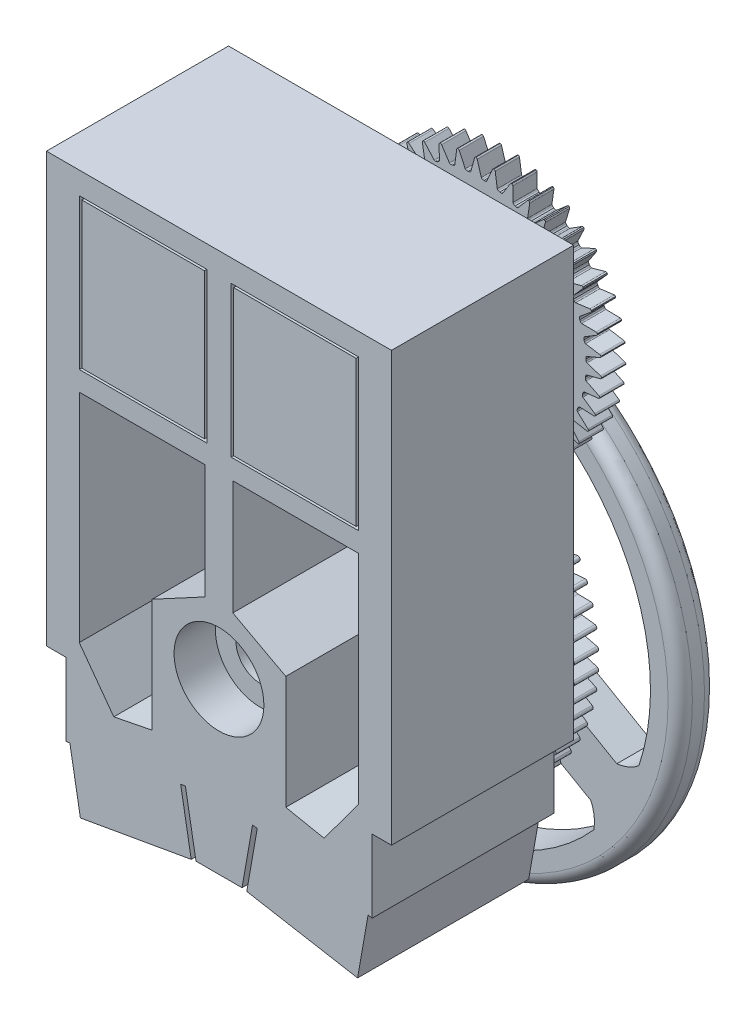
SolidWorks part; units mm, degrees
ref_plane "前视基准面" through (0, 0, 0) normal (0, 0, 1) x (1, 0, 0)
ref_plane "上视基准面" through (0, 0, 0) normal (0, 1, 0) x (1, 0, 0)
ref_plane "右视基准面" through (0, 0, 0) normal (1, 0, 0) x (0, 0, -1)
sketch "草图1" plane through (0, 0, 0) normal (0, 0, 1) x (1, 0, 0)
  line L0 (14.2131, -21.082) -> (12.6181, -21.082)
  line L2 (-11.5, 12.4) -> (-1, 12.4)
  line L3 (-11.5, 12.4) -> (-11.5, 0)
  line L4 (-11.5, 0) -> (-1, 0)
  line L5 (-1, 12.4) -> (-1, 0)
  line L6 (14.2131, 14.2258) -> (14.2131, -1.4738)
  line L7 (11.5, 0) -> (1, 0)
  line L8 (14.2131, 14.2258) -> (-14.2131, 14.2258)
  line L9 (-14.2131, 14.2258) -> (-14.2131, -1.4738)
  line L12 (1, 12.4) -> (1, 0)
  line L13 (11.5, 12.4) -> (1, 12.4)
  line L14 (11.5, 12.4) -> (11.5, 0)
  line L16 (14.2131, -1.4738) -> (14.2131, -21.082)
  line L18 (-14.2131, -1.4738) -> (-14.2131, -21.082)
  line L19 (-12.6181, -21.082) -> (-14.2131, -21.082)
  line L24 (-1.897, -30.2746) -> (1.897, -30.2746)
  line L29 (1.897, -30.2746) -> (2.7652, -25.3506)
  line L30 (2.7652, -25.3506) -> (12.6181, -27.0879)
  line L31 (12.6181, -27.0879) -> (12.6181, -21.082)
  line L32 (-1.897, -30.2746) -> (-2.7652, -25.3506)
  line L33 (-2.7652, -25.3506) -> (-12.6181, -27.0879)
  line L34 (-12.6181, -27.0879) -> (-12.6181, -21.082)
  circle A0 centre (0, -16.3459) radius 2
  point P8 (-1.6019, -21.082)
  dimension "D5" = 4
  dimension "D1" = 10.5
  dimension "D2" = 12.4
  dimension "D3" = 28.4262
  dimension "D4" = 0
  dimension "D6" = 5
extrude "凸台-拉伸1" add sketch "草图1" along normal blind 15
sketch "草图2" plane through (0, 0, 15) normal (0, 0, 1) x (1, 0, 0)
  circle A0 centre (0, -16.3459) radius 3.7
extrude "切除-拉伸1" cut sketch "草图2" against normal blind 3.4
sketch "草图3" plane through (0, 0, 0) normal (0, 0, -1) x (-1, 0, 0)
  circle A0 centre (0, -16.3459) radius 3.7
  dimension "D1" = 7.4
extrude "切除-拉伸2" cut sketch "草图3" against normal blind 3.4
sketch "草图4" plane through (0, 0, 15) normal (0, 0, 1) x (1, 0, 0)
  line L1 (-11.511, -1.6162) -> (-1.141, -1.6162)
  line L2 (-1.141, -1.6162) -> (-1.141, -11.0446)
  line L3 (-1.141, -11.0446) -> (-5.5022, -13.39)
  line L4 (-5.5022, -13.39) -> (-5.5022, -22.7344)
  line L5 (-5.5022, -22.7344) -> (-8.6655, -23.3615)
  line L6 (-11.511, -19.4847) -> (-11.511, -1.6162)
  line L7 (5.5022, -22.7344) -> (8.6655, -23.3615)
  line L8 (5.5022, -13.39) -> (5.5022, -22.7344)
  line L9 (1.141, -11.0446) -> (5.5022, -13.39)
  line L10 (1.141, -1.6162) -> (1.141, -11.0446)
  line L11 (11.511, -1.6162) -> (1.141, -1.6162)
  line L12 (11.511, -19.4847) -> (11.511, -1.6162)
  line L13 (11.511, -19.4847) -> (8.6655, -23.3615)
  line L14 (-11.511, -19.4847) -> (-8.6655, -23.3615)
extrude "切除-拉伸4" cut sketch "草图4" against normal blind 30
sketch "草图5" plane through (0, 0, 0) normal (0, 0, 1) x (1, 0, 0)
  line L0 (-11.3, 12.2) -> (-11.3, 0.2)
  line L5 (-11.3, 0.2) -> (-1.2, 0.2)
  line L6 (-1.2, 12.2) -> (-1.2, 0.2)
  line L7 (-11.3, 12.2) -> (-1.2, 12.2)
  line L9 (11.3, 12.2) -> (1.2, 12.2)
  line L10 (1.2, 12.2) -> (1.2, 0.2)
  line L11 (11.3, 0.2) -> (1.2, 0.2)
  line L12 (11.3, 12.2) -> (11.3, 0.2)
extrude "凸台-拉伸2" add sketch "草图5" along normal blind 15 separate body
sketch "草图6" plane through (0, 0, 0) normal (0, 0, -1) x (-1, 0, 0)
  line L5 (0.5574, -2.1882) -> (0.2083, -3.1894)
  line L6 (-0.5574, -2.1882) -> (-0.2083, -3.1894)
  line L7 (0.9255, -2.2075) -> (1.1681, -3.2397)
  line L9 (-0.9255, -2.2075) -> (-1.1681, -3.2397)
  line L10 (2.0343, -2.324) -> (1.5824, -3.2833)
  line L11 (2.3983, -2.3816) -> (2.5316, -3.4336)
  line L12 (3.4888, -2.6134) -> (2.9391, -3.5202)
  line L13 (3.8448, -2.7088) -> (3.8675, -3.769)
  line L14 (4.9051, -3.0534) -> (4.2637, -3.8977)
  line L15 (5.2492, -3.1854) -> (5.1609, -4.2421)
  line L16 (6.2677, -3.6389) -> (5.5415, -4.4116)
  line L17 (6.5961, -3.8062) -> (6.3978, -4.8479)
  line L18 (7.5616, -4.3637) -> (6.7586, -5.0562)
  line L19 (7.8707, -4.5644) -> (7.5647, -5.5797)
  line L20 (8.7727, -5.2197) -> (7.9017, -5.8245)
  line L21 (9.0591, -5.4517) -> (8.6486, -6.4294)
  line L22 (9.8876, -6.1977) -> (8.9582, -6.7081)
  line L23 (10.1483, -6.4583) -> (9.6378, -7.3877)
  line L24 (10.8943, -7.2868) -> (9.9166, -7.6973)
  line L25 (11.1262, -7.5732) -> (10.5214, -8.4442)
  line L26 (11.7815, -8.4752) -> (10.7663, -8.7813)
  line L27 (11.9823, -8.7843) -> (11.2897, -9.5873)
  line L28 (12.5397, -9.7498) -> (11.498, -9.9481)
  line L29 (12.707, -10.0782) -> (11.9343, -10.8044)
  line L30 (13.1605, -11.0967) -> (12.1038, -11.185)
  line L31 (13.2926, -11.4408) -> (12.4482, -12.0822)
  line L32 (13.6371, -12.5011) -> (12.5769, -12.4785)
  line L33 (13.7325, -12.8571) -> (12.8257, -13.4068)
  line L34 (13.9643, -13.9476) -> (12.9123, -13.8143)
  line L35 (14.0219, -14.3116) -> (13.0626, -14.7635)
  line L36 (14.1385, -15.4204) -> (13.1062, -15.1779)
  line L37 (14.1578, -15.7885) -> (13.1565, -16.1376)
  line L38 (14.1578, -16.9034) -> (13.1565, -16.5542)
  line L39 (14.1385, -17.2714) -> (13.1062, -17.514)
  line L40 (14.0219, -18.3802) -> (13.0626, -17.9283)
  line L41 (13.9643, -18.7442) -> (12.9123, -18.8776)
  line L42 (13.7325, -19.8347) -> (12.8257, -19.2851)
  line L43 (13.6371, -20.1907) -> (12.5769, -20.2134)
  line L44 (13.2926, -21.2511) -> (12.4482, -20.6096)
  line L45 (13.1605, -21.5951) -> (12.1038, -21.5068)
  line L46 (12.707, -22.6136) -> (11.9343, -21.8874)
  line L47 (12.5397, -22.942) -> (11.498, -22.7438)
  line L48 (11.9823, -23.9076) -> (11.2897, -23.1046)
  line L49 (11.7815, -24.2167) -> (10.7663, -23.9106)
  line L50 (11.1262, -25.1186) -> (10.5214, -24.2476)
  line L51 (10.8943, -25.405) -> (9.9166, -24.9945)
  line L52 (10.1483, -26.2336) -> (9.6378, -25.3041)
  line L53 (9.8876, -26.4942) -> (8.9582, -25.9837)
  line L54 (9.0591, -27.2402) -> (8.6486, -26.2625)
  line L55 (8.7727, -27.4721) -> (7.9017, -26.8673)
  line L56 (7.8707, -28.1274) -> (7.5647, -27.1122)
  line L57 (7.5616, -28.3282) -> (6.7586, -27.6356)
  line L58 (6.5961, -28.8856) -> (6.3978, -27.8439)
  line L59 (6.2677, -29.0529) -> (5.5415, -28.2802)
  line L60 (5.2492, -29.5064) -> (5.1609, -28.4497)
  line L61 (4.9051, -29.6385) -> (4.2637, -28.7941)
  line L62 (3.8448, -29.983) -> (3.8675, -28.9229)
  line L63 (3.4888, -30.0784) -> (2.9391, -29.1716)
  line L64 (2.3983, -30.3102) -> (2.5316, -29.2582)
  line L65 (2.0343, -30.3678) -> (1.5824, -29.4086)
  line L66 (0.9255, -30.4844) -> (1.1681, -29.4521)
  line L67 (0.5574, -30.5037) -> (0.2083, -29.5024)
  line L68 (-0.5574, -30.5037) -> (-0.2083, -29.5024)
  line L69 (-0.9255, -30.4844) -> (-1.1681, -29.4521)
  line L70 (-2.0343, -30.3678) -> (-1.5824, -29.4086)
  line L71 (-2.3983, -30.3102) -> (-2.5316, -29.2582)
  line L72 (-3.4888, -30.0784) -> (-2.9391, -29.1716)
  line L73 (-3.8448, -29.983) -> (-3.8675, -28.9229)
  line L74 (-4.9051, -29.6385) -> (-4.2637, -28.7941)
  line L75 (-5.2492, -29.5064) -> (-5.1609, -28.4497)
  line L76 (-6.2677, -29.0529) -> (-5.5415, -28.2802)
  line L77 (-6.5961, -28.8856) -> (-6.3978, -27.8439)
  line L78 (-7.5616, -28.3282) -> (-6.7586, -27.6356)
  line L79 (-7.8707, -28.1274) -> (-7.5647, -27.1122)
  line L80 (-8.7727, -27.4721) -> (-7.9017, -26.8673)
  line L81 (-9.0591, -27.2402) -> (-8.6486, -26.2625)
  line L82 (-9.8876, -26.4942) -> (-8.9582, -25.9837)
  line L83 (-10.1483, -26.2336) -> (-9.6378, -25.3041)
  line L84 (-10.8943, -25.405) -> (-9.9166, -24.9945)
  line L85 (-11.1262, -25.1186) -> (-10.5214, -24.2476)
  line L86 (-11.7815, -24.2167) -> (-10.7663, -23.9106)
  line L87 (-11.9823, -23.9076) -> (-11.2897, -23.1046)
  line L88 (-12.5397, -22.942) -> (-11.498, -22.7438)
  line L89 (-12.707, -22.6136) -> (-11.9343, -21.8874)
  line L90 (-13.1605, -21.5951) -> (-12.1038, -21.5068)
  line L91 (-13.2926, -21.2511) -> (-12.4482, -20.6096)
  line L92 (-13.6371, -20.1907) -> (-12.5769, -20.2134)
  line L93 (-13.7325, -19.8347) -> (-12.8257, -19.2851)
  line L94 (-13.9643, -18.7442) -> (-12.9123, -18.8776)
  line L95 (-14.0219, -18.3802) -> (-13.0626, -17.9283)
  line L96 (-14.1385, -17.2714) -> (-13.1062, -17.514)
  line L97 (-14.1578, -16.9034) -> (-13.1565, -16.5542)
  line L98 (-14.1578, -15.7885) -> (-13.1565, -16.1376)
  line L99 (-14.1385, -15.4204) -> (-13.1062, -15.1779)
  line L100 (-14.0219, -14.3116) -> (-13.0626, -14.7635)
  line L101 (-13.9643, -13.9476) -> (-12.9123, -13.8143)
  line L102 (-13.7325, -12.8571) -> (-12.8257, -13.4068)
  line L103 (-13.6371, -12.5011) -> (-12.5769, -12.4785)
  line L104 (-13.2926, -11.4408) -> (-12.4482, -12.0822)
  line L105 (-13.1605, -11.0967) -> (-12.1038, -11.185)
  line L106 (-12.707, -10.0782) -> (-11.9343, -10.8044)
  line L107 (-12.5397, -9.7498) -> (-11.498, -9.9481)
  line L108 (-11.9823, -8.7843) -> (-11.2897, -9.5873)
  line L109 (-11.7815, -8.4752) -> (-10.7663, -8.7813)
  line L110 (-11.1262, -7.5732) -> (-10.5214, -8.4442)
  line L111 (-10.8943, -7.2868) -> (-9.9166, -7.6973)
  line L112 (-10.1483, -6.4583) -> (-9.6378, -7.3877)
  line L113 (-9.8876, -6.1977) -> (-8.9582, -6.7081)
  line L114 (-9.0591, -5.4517) -> (-8.6486, -6.4294)
  line L115 (-8.7727, -5.2197) -> (-7.9017, -5.8245)
  line L116 (-7.8707, -4.5644) -> (-7.5647, -5.5797)
  line L117 (-7.5616, -4.3637) -> (-6.7586, -5.0562)
  line L118 (-6.5961, -3.8062) -> (-6.3978, -4.8479)
  line L119 (-6.2677, -3.6389) -> (-5.5415, -4.4116)
  line L120 (-5.2492, -3.1854) -> (-5.1609, -4.2421)
  line L121 (-4.9051, -3.0534) -> (-4.2637, -3.8977)
  line L122 (-3.8448, -2.7088) -> (-3.8675, -3.769)
  line L123 (-3.4888, -2.6134) -> (-2.9391, -3.5202)
  line L124 (-2.3983, -2.3816) -> (-2.5316, -3.4336)
  line L125 (-2.0343, -2.324) -> (-1.5824, -3.2833)
  arc A1 (-1.3589, -3.4171) -> (-1.1681, -3.2397) centre (-1.3815, -3.2014) ccw
  arc A2 (-0.9255, -2.2075) -> (-0.5574, -2.1882) centre (-0.7383, -2.2588) cw
  arc A3 (0, -3.3459) -> (-0.2083, -3.1894) centre (0, -3.129) cw
  arc A4 (0, -3.3459) -> (0.2083, -3.1894) centre (0, -3.129) ccw
  arc A5 (1.3589, -3.4171) -> (1.1681, -3.2397) centre (1.3815, -3.2014) cw
  arc A6 (0.5574, -2.1882) -> (0.9255, -2.2075) centre (0.7383, -2.2588) cw
  arc A7 (1.3589, -3.4171) -> (1.5824, -3.2833) centre (1.3815, -3.2014) ccw
  arc A8 (2.7029, -3.63) -> (2.5316, -3.4336) centre (2.7479, -3.4179) cw
  arc A9 (2.0343, -2.324) -> (2.3983, -2.3816) centre (2.2067, -2.4131) cw
  arc A10 (2.7029, -3.63) -> (2.9391, -3.5202) centre (2.7479, -3.4179) ccw
  arc A11 (4.0172, -3.9822) -> (3.8675, -3.769) centre (4.0842, -3.7759) cw
  arc A12 (3.4888, -2.6134) -> (3.8448, -2.7088) centre (3.651, -2.7201) cw
  arc A13 (4.0172, -3.9822) -> (4.2637, -3.8977) centre (4.0842, -3.7759) ccw
  arc A14 (5.2876, -4.4698) -> (5.1609, -4.2421) centre (5.3758, -4.2717) cw
  arc A15 (4.9051, -3.0534) -> (5.2492, -3.1854) centre (5.0553, -3.1764) cw
  arc A16 (5.2876, -4.4698) -> (5.5415, -4.4116) centre (5.3758, -4.2717) ccw
  arc A17 (6.5, -5.0876) -> (6.3978, -4.8479) centre (6.6084, -4.8998) cw
  arc A18 (6.2677, -3.6389) -> (6.5961, -3.8062) centre (6.4042, -3.7769) cw
  arc A19 (6.5, -5.0876) -> (6.7586, -5.0562) centre (6.6084, -4.8998) ccw
  arc A20 (7.6412, -5.8287) -> (7.5647, -5.5797) centre (7.7687, -5.6532) cw
  arc A21 (7.5616, -4.3637) -> (7.8707, -4.5644) centre (7.6829, -4.5152) cw
  arc A22 (7.6412, -5.8287) -> (7.9017, -5.8245) centre (7.7687, -5.6532) ccw
  arc A23 (8.6987, -6.685) -> (8.6486, -6.4294) centre (8.8438, -6.5239) cw
  arc A24 (8.7727, -5.2197) -> (9.0591, -5.4517) centre (8.8775, -5.3831) cw
  arc A25 (8.6987, -6.685) -> (8.9582, -6.7081) centre (8.8438, -6.5239) ccw
  arc A26 (9.6609, -7.6472) -> (9.6378, -7.3877) centre (9.8221, -7.5021) cw
  arc A27 (9.8876, -6.1977) -> (10.1483, -6.4583) centre (9.9748, -6.3711) cw
  arc A28 (9.6609, -7.6472) -> (9.9166, -7.6973) centre (9.8221, -7.5021) ccw
  arc A29 (10.5172, -8.7047) -> (10.5214, -8.4442) centre (10.6927, -8.5772) cw
  arc A30 (10.8943, -7.2868) -> (11.1262, -7.5732) centre (10.9628, -7.4684) cw
  arc A31 (10.5172, -8.7047) -> (10.7663, -8.7813) centre (10.6927, -8.5772) ccw
  arc A32 (11.2583, -9.8459) -> (11.2897, -9.5873) centre (11.4462, -9.7375) cw
  arc A33 (11.7815, -8.4752) -> (11.9823, -8.7843) centre (11.8307, -8.663) cw
  arc A34 (11.2583, -9.8459) -> (11.498, -9.9481) centre (11.4462, -9.7375) ccw
  arc A35 (11.8761, -11.0583) -> (11.9343, -10.8044) centre (12.0742, -10.9701) cw
  arc A36 (12.5397, -9.7498) -> (12.707, -10.0782) centre (12.569, -9.9417) cw
  arc A37 (11.8761, -11.0583) -> (12.1038, -11.185) centre (12.0742, -10.9701) ccw
  arc A38 (12.3637, -12.3287) -> (12.4482, -12.0822) centre (12.57, -12.2617) cw
  arc A39 (13.1605, -11.0967) -> (13.2926, -11.4408) centre (13.1695, -11.2906) cw
  arc A40 (12.3637, -12.3287) -> (12.5769, -12.4785) centre (12.57, -12.2617) ccw
  arc A41 (12.7159, -13.6431) -> (12.8257, -13.4068) centre (12.9281, -13.598) cw
  arc A42 (13.6371, -12.5011) -> (13.7325, -12.8571) centre (13.6258, -12.6949) cw
  arc A43 (12.7159, -13.6431) -> (12.9123, -13.8143) centre (12.9281, -13.598) ccw
  arc A44 (12.9288, -14.987) -> (13.0626, -14.7635) centre (13.1445, -14.9644) cw
  arc A45 (13.9643, -13.9476) -> (14.0219, -14.3116) centre (13.9328, -14.1392) cw
  arc A46 (12.9288, -14.987) -> (13.1062, -15.1779) centre (13.1445, -14.9644) ccw
  arc A47 (13, -16.3459) -> (13.1565, -16.1376) centre (13.2169, -16.3459) cw
  arc A48 (14.1385, -15.4204) -> (14.1578, -15.7885) centre (14.0872, -15.6076) cw
  arc A49 (13, -16.3459) -> (13.1565, -16.5542) centre (13.2169, -16.3459) ccw
  arc A50 (12.9288, -17.7048) -> (13.1062, -17.514) centre (13.1445, -17.7275) cw
  arc A51 (14.1578, -16.9034) -> (14.1385, -17.2714) centre (14.0872, -17.0842) cw
  arc A52 (12.9288, -17.7048) -> (13.0626, -17.9283) centre (13.1445, -17.7275) ccw
  arc A53 (12.7159, -19.0488) -> (12.9123, -18.8776) centre (12.9281, -19.0939) cw
  arc A54 (14.0219, -18.3802) -> (13.9643, -18.7442) centre (13.9328, -18.5527) cw
  arc A55 (12.7159, -19.0488) -> (12.8257, -19.2851) centre (12.9281, -19.0939) ccw
  arc A56 (12.3637, -20.3631) -> (12.5769, -20.2134) centre (12.57, -20.4302) cw
  arc A57 (13.7325, -19.8347) -> (13.6371, -20.1907) centre (13.6258, -19.9969) cw
  arc A58 (12.3637, -20.3631) -> (12.4482, -20.6096) centre (12.57, -20.4302) ccw
  arc A59 (11.8761, -21.6335) -> (12.1038, -21.5068) centre (12.0742, -21.7217) cw
  arc A60 (13.2926, -21.2511) -> (13.1605, -21.5951) centre (13.1695, -21.4012) cw
  arc A61 (11.8761, -21.6335) -> (11.9343, -21.8874) centre (12.0742, -21.7217) ccw
  arc A62 (11.2583, -22.8459) -> (11.498, -22.7438) centre (11.4462, -22.9544) cw
  arc A63 (12.707, -22.6136) -> (12.5397, -22.942) centre (12.569, -22.7501) cw
  arc A64 (11.2583, -22.8459) -> (11.2897, -23.1046) centre (11.4462, -22.9544) ccw
  arc A65 (10.5172, -23.9871) -> (10.7663, -23.9106) centre (10.6927, -24.1146) cw
  arc A66 (11.9823, -23.9076) -> (11.7815, -24.2167) centre (11.8307, -24.0289) cw
  arc A67 (10.5172, -23.9871) -> (10.5214, -24.2476) centre (10.6927, -24.1146) ccw
  arc A68 (9.6609, -25.0446) -> (9.9166, -24.9945) centre (9.8221, -25.1897) cw
  arc A69 (11.1262, -25.1186) -> (10.8943, -25.405) centre (10.9628, -25.2234) cw
  arc A70 (9.6609, -25.0446) -> (9.6378, -25.3041) centre (9.8221, -25.1897) ccw
  arc A71 (8.6987, -26.0068) -> (8.9582, -25.9837) centre (8.8438, -26.168) cw
  arc A72 (10.1483, -26.2336) -> (9.8876, -26.4942) centre (9.9748, -26.3207) cw
  arc A73 (8.6987, -26.0068) -> (8.6486, -26.2625) centre (8.8438, -26.168) ccw
  arc A74 (7.6412, -26.8631) -> (7.9017, -26.8673) centre (7.7687, -27.0386) cw
  arc A75 (9.0591, -27.2402) -> (8.7727, -27.4721) centre (8.8775, -27.3087) cw
  arc A76 (7.6412, -26.8631) -> (7.5647, -27.1122) centre (7.7687, -27.0386) ccw
  arc A77 (6.5, -27.6043) -> (6.7586, -27.6356) centre (6.6084, -27.7921) cw
  arc A78 (7.8707, -28.1274) -> (7.5616, -28.3282) centre (7.6829, -28.1766) cw
  arc A79 (6.5, -27.6043) -> (6.3978, -27.8439) centre (6.6084, -27.7921) ccw
  arc A80 (5.2876, -28.222) -> (5.5415, -28.2802) centre (5.3758, -28.4201) cw
  arc A81 (6.5961, -28.8856) -> (6.2677, -29.0529) centre (6.4042, -28.9149) cw
  arc A82 (5.2876, -28.222) -> (5.1609, -28.4497) centre (5.3758, -28.4201) ccw
  arc A83 (4.0172, -28.7097) -> (4.2637, -28.7941) centre (4.0842, -28.9159) cw
  arc A84 (5.2492, -29.5064) -> (4.9051, -29.6385) centre (5.0553, -29.5155) cw
  arc A85 (4.0172, -28.7097) -> (3.8675, -28.9229) centre (4.0842, -28.9159) ccw
  arc A86 (2.7029, -29.0618) -> (2.9391, -29.1716) centre (2.7479, -29.274) cw
  arc A87 (3.8448, -29.983) -> (3.4888, -30.0784) centre (3.651, -29.9717) cw
  arc A88 (2.7029, -29.0618) -> (2.5316, -29.2582) centre (2.7479, -29.274) ccw
  arc A89 (1.3589, -29.2747) -> (1.5824, -29.4086) centre (1.3815, -29.4904) cw
  arc A90 (2.3983, -30.3102) -> (2.0343, -30.3678) centre (2.2067, -30.2787) cw
  arc A91 (1.3589, -29.2747) -> (1.1681, -29.4521) centre (1.3815, -29.4904) ccw
  arc A92 (0, -29.3459) -> (0.2083, -29.5024) centre (0, -29.5628) cw
  arc A93 (0.9255, -30.4844) -> (0.5574, -30.5037) centre (0.7383, -30.4331) cw
  arc A94 (0, -29.3459) -> (-0.2083, -29.5024) centre (0, -29.5628) ccw
  arc A95 (-1.3589, -29.2747) -> (-1.1681, -29.4521) centre (-1.3815, -29.4904) cw
  arc A96 (-0.5574, -30.5037) -> (-0.9255, -30.4844) centre (-0.7383, -30.4331) cw
  arc A97 (-1.3589, -29.2747) -> (-1.5824, -29.4086) centre (-1.3815, -29.4904) ccw
  arc A98 (-2.7029, -29.0618) -> (-2.5316, -29.2582) centre (-2.7479, -29.274) cw
  arc A99 (-2.0343, -30.3678) -> (-2.3983, -30.3102) centre (-2.2067, -30.2787) cw
  arc A100 (-2.7029, -29.0618) -> (-2.9391, -29.1716) centre (-2.7479, -29.274) ccw
  arc A101 (-4.0172, -28.7097) -> (-3.8675, -28.9229) centre (-4.0842, -28.9159) cw
  arc A102 (-3.4888, -30.0784) -> (-3.8448, -29.983) centre (-3.651, -29.9717) cw
  arc A103 (-4.0172, -28.7097) -> (-4.2637, -28.7941) centre (-4.0842, -28.9159) ccw
  arc A104 (-5.2876, -28.222) -> (-5.1609, -28.4497) centre (-5.3758, -28.4201) cw
  arc A105 (-4.9051, -29.6385) -> (-5.2492, -29.5064) centre (-5.0553, -29.5155) cw
  arc A106 (-5.2876, -28.222) -> (-5.5415, -28.2802) centre (-5.3758, -28.4201) ccw
  arc A107 (-6.5, -27.6043) -> (-6.3978, -27.8439) centre (-6.6084, -27.7921) cw
  arc A108 (-6.2677, -29.0529) -> (-6.5961, -28.8856) centre (-6.4042, -28.9149) cw
  arc A109 (-6.5, -27.6043) -> (-6.7586, -27.6356) centre (-6.6084, -27.7921) ccw
  arc A110 (-7.6412, -26.8631) -> (-7.5647, -27.1122) centre (-7.7687, -27.0386) cw
  arc A111 (-7.5616, -28.3282) -> (-7.8707, -28.1274) centre (-7.6829, -28.1766) cw
  arc A112 (-7.6412, -26.8631) -> (-7.9017, -26.8673) centre (-7.7687, -27.0386) ccw
  arc A113 (-8.6987, -26.0068) -> (-8.6486, -26.2625) centre (-8.8438, -26.168) cw
  arc A114 (-8.7727, -27.4721) -> (-9.0591, -27.2402) centre (-8.8775, -27.3087) cw
  arc A115 (-8.6987, -26.0068) -> (-8.9582, -25.9837) centre (-8.8438, -26.168) ccw
  arc A116 (-9.6609, -25.0446) -> (-9.6378, -25.3041) centre (-9.8221, -25.1897) cw
  arc A117 (-9.8876, -26.4942) -> (-10.1483, -26.2336) centre (-9.9748, -26.3207) cw
  arc A118 (-9.6609, -25.0446) -> (-9.9166, -24.9945) centre (-9.8221, -25.1897) ccw
  arc A119 (-10.5172, -23.9871) -> (-10.5214, -24.2476) centre (-10.6927, -24.1146) cw
  arc A120 (-10.8943, -25.405) -> (-11.1262, -25.1186) centre (-10.9628, -25.2234) cw
  arc A121 (-10.5172, -23.9871) -> (-10.7663, -23.9106) centre (-10.6927, -24.1146) ccw
  arc A122 (-11.2583, -22.8459) -> (-11.2897, -23.1046) centre (-11.4462, -22.9544) cw
  arc A123 (-11.7815, -24.2167) -> (-11.9823, -23.9076) centre (-11.8307, -24.0289) cw
  arc A124 (-11.2583, -22.8459) -> (-11.498, -22.7438) centre (-11.4462, -22.9544) ccw
  arc A125 (-11.8761, -21.6335) -> (-11.9343, -21.8874) centre (-12.0742, -21.7217) cw
  arc A126 (-12.5397, -22.942) -> (-12.707, -22.6136) centre (-12.569, -22.7501) cw
  arc A127 (-11.8761, -21.6335) -> (-12.1038, -21.5068) centre (-12.0742, -21.7217) ccw
  arc A128 (-12.3637, -20.3631) -> (-12.4482, -20.6096) centre (-12.57, -20.4302) cw
  arc A129 (-13.1605, -21.5951) -> (-13.2926, -21.2511) centre (-13.1695, -21.4012) cw
  arc A130 (-12.3637, -20.3631) -> (-12.5769, -20.2134) centre (-12.57, -20.4302) ccw
  arc A131 (-12.7159, -19.0488) -> (-12.8257, -19.2851) centre (-12.9281, -19.0939) cw
  arc A132 (-13.6371, -20.1907) -> (-13.7325, -19.8347) centre (-13.6258, -19.9969) cw
  arc A133 (-12.7159, -19.0488) -> (-12.9123, -18.8776) centre (-12.9281, -19.0939) ccw
  arc A134 (-12.9288, -17.7048) -> (-13.0626, -17.9283) centre (-13.1445, -17.7275) cw
  arc A135 (-13.9643, -18.7442) -> (-14.0219, -18.3802) centre (-13.9328, -18.5527) cw
  arc A136 (-12.9288, -17.7048) -> (-13.1062, -17.514) centre (-13.1445, -17.7275) ccw
  arc A137 (-13, -16.3459) -> (-13.1565, -16.5542) centre (-13.2169, -16.3459) cw
  arc A138 (-14.1385, -17.2714) -> (-14.1578, -16.9034) centre (-14.0872, -17.0842) cw
  arc A139 (-13, -16.3459) -> (-13.1565, -16.1376) centre (-13.2169, -16.3459) ccw
  arc A140 (-12.9288, -14.987) -> (-13.1062, -15.1779) centre (-13.1445, -14.9644) cw
  arc A141 (-14.1578, -15.7885) -> (-14.1385, -15.4204) centre (-14.0872, -15.6076) cw
  arc A142 (-12.9288, -14.987) -> (-13.0626, -14.7635) centre (-13.1445, -14.9644) ccw
  arc A143 (-12.7159, -13.6431) -> (-12.9123, -13.8143) centre (-12.9281, -13.598) cw
  arc A144 (-14.0219, -14.3116) -> (-13.9643, -13.9476) centre (-13.9328, -14.1392) cw
  arc A145 (-12.7159, -13.6431) -> (-12.8257, -13.4068) centre (-12.9281, -13.598) ccw
  arc A146 (-12.3637, -12.3287) -> (-12.5769, -12.4785) centre (-12.57, -12.2617) cw
  arc A147 (-13.7325, -12.8571) -> (-13.6371, -12.5011) centre (-13.6258, -12.6949) cw
  arc A148 (-12.3637, -12.3287) -> (-12.4482, -12.0822) centre (-12.57, -12.2617) ccw
  arc A149 (-11.8761, -11.0583) -> (-12.1038, -11.185) centre (-12.0742, -10.9701) cw
  arc A150 (-13.2926, -11.4408) -> (-13.1605, -11.0967) centre (-13.1695, -11.2906) cw
  arc A151 (-11.8761, -11.0583) -> (-11.9343, -10.8044) centre (-12.0742, -10.9701) ccw
  arc A152 (-11.2583, -9.8459) -> (-11.498, -9.9481) centre (-11.4462, -9.7375) cw
  arc A153 (-12.707, -10.0782) -> (-12.5397, -9.7498) centre (-12.569, -9.9417) cw
  arc A154 (-11.2583, -9.8459) -> (-11.2897, -9.5873) centre (-11.4462, -9.7375) ccw
  arc A155 (-10.5172, -8.7047) -> (-10.7663, -8.7813) centre (-10.6927, -8.5772) cw
  arc A156 (-11.9823, -8.7843) -> (-11.7815, -8.4752) centre (-11.8307, -8.663) cw
  arc A157 (-10.5172, -8.7047) -> (-10.5214, -8.4442) centre (-10.6927, -8.5772) ccw
  arc A158 (-9.6609, -7.6472) -> (-9.9166, -7.6973) centre (-9.8221, -7.5021) cw
  arc A159 (-11.1262, -7.5732) -> (-10.8943, -7.2868) centre (-10.9628, -7.4684) cw
  arc A160 (-9.6609, -7.6472) -> (-9.6378, -7.3877) centre (-9.8221, -7.5021) ccw
  arc A161 (-8.6987, -6.685) -> (-8.9582, -6.7081) centre (-8.8438, -6.5239) cw
  arc A162 (-10.1483, -6.4583) -> (-9.8876, -6.1977) centre (-9.9748, -6.3711) cw
  arc A163 (-8.6987, -6.685) -> (-8.6486, -6.4294) centre (-8.8438, -6.5239) ccw
  arc A164 (-7.6412, -5.8287) -> (-7.9017, -5.8245) centre (-7.7687, -5.6532) cw
  arc A165 (-9.0591, -5.4517) -> (-8.7727, -5.2197) centre (-8.8775, -5.3831) cw
  arc A166 (-7.6412, -5.8287) -> (-7.5647, -5.5797) centre (-7.7687, -5.6532) ccw
  arc A167 (-6.5, -5.0876) -> (-6.7586, -5.0562) centre (-6.6084, -4.8998) cw
  arc A168 (-7.8707, -4.5644) -> (-7.5616, -4.3637) centre (-7.6829, -4.5152) cw
  arc A169 (-6.5, -5.0876) -> (-6.3978, -4.8479) centre (-6.6084, -4.8998) ccw
  arc A170 (-5.2876, -4.4698) -> (-5.5415, -4.4116) centre (-5.3758, -4.2717) cw
  arc A171 (-6.5961, -3.8062) -> (-6.2677, -3.6389) centre (-6.4042, -3.7769) cw
  arc A172 (-5.2876, -4.4698) -> (-5.1609, -4.2421) centre (-5.3758, -4.2717) ccw
  arc A173 (-4.0172, -3.9822) -> (-4.2637, -3.8977) centre (-4.0842, -3.7759) cw
  arc A174 (-5.2492, -3.1854) -> (-4.9051, -3.0534) centre (-5.0553, -3.1764) cw
  arc A175 (-4.0172, -3.9822) -> (-3.8675, -3.769) centre (-4.0842, -3.7759) ccw
  arc A176 (-2.7029, -3.63) -> (-2.9391, -3.5202) centre (-2.7479, -3.4179) cw
  arc A177 (-3.8448, -2.7088) -> (-3.4888, -2.6134) centre (-3.651, -2.7201) cw
  arc A178 (-2.7029, -3.63) -> (-2.5316, -3.4336) centre (-2.7479, -3.4179) ccw
  arc A179 (-1.3589, -3.4171) -> (-1.5824, -3.2833) centre (-1.3815, -3.2014) cw
  arc A180 (-2.3983, -2.3816) -> (-2.0343, -2.324) centre (-2.2067, -2.4131) cw
  circle A181 centre (0, -16.3459) radius 2
  point P545 (0, -16.3459)
  dimension "D2" = 60
extrude "凸台-拉伸6" add sketch "草图6" along normal blind 2 separate body
sketch "草图7" plane through (0, 0, 0) normal (0, 0, -1) x (-1, 0, 0)
  line L0 (-11.3, 6.2) -> (-1.2, 6.2)
  line L1 (-11.3, 0.2) -> (-11.3, 12.2) construction
  line L2 (-1.2, 12.2) -> (-1.2, 0.2) construction
  line L3 (-4.7758, -2.747) -> (-4.2184, -3.7844)
  line L4 (-4.8878, -2.6931) -> (-5.0141, -2.6931)
  line L6 (-3.9278, -2.5652) -> (-4.0111, -3.74)
  line L7 (-3.8477, -2.4702) -> (-3.7325, -2.4184)
  line L8 (-6.0942, -2.8663) -> (-5.6938, -3.9738)
  line L9 (-5.2288, -2.8099) -> (-5.4822, -3.96)
  line L10 (-6.1972, -2.7967) -> (-6.3222, -2.7783)
  line L11 (-5.1357, -2.7276) -> (-5.0141, -2.6931)
  line L12 (-7.4159, -2.7924) -> (-7.181, -3.9464)
  line L13 (-6.5516, -2.8626) -> (-6.9697, -3.9636)
  line L14 (-7.5077, -2.7085) -> (-7.6286, -2.6721)
  line L15 (-6.4474, -2.7947) -> (-6.3222, -2.7783)
  line L16 (-8.7128, -2.5268) -> (-8.6484, -3.7027)
  line L17 (-7.8679, -2.7221) -> (-8.4419, -3.7505)
  line L18 (-8.7913, -2.4305) -> (-8.9057, -2.3768)
  line L19 (-7.755, -2.6701) -> (-7.6286, -2.6721)
  line L20 (-9.9571, -2.0752) -> (-10.0647, -3.248)
  line L21 (-9.1497, -2.3915) -> (-9.8673, -3.3253)
  line L22 (-10.0209, -1.9685) -> (-10.1262, -1.8988)
  line L23 (-9.0304, -2.3564) -> (-8.9057, -2.3768)
  line L24 (-11.1225, -1.4473) -> (-11.3997, -2.5919)
  line L25 (-10.3697, -1.8777) -> (-11.2157, -2.6971)
  line L26 (-11.17, -1.3324) -> (-11.2641, -1.2481)
  line L27 (-10.2466, -1.8604) -> (-10.1262, -1.8988)
  line L28 (-12.184, -0.6563) -> (-12.6249, -1.7484)
  line L29 (-11.502, -1.1918) -> (-12.4582, -1.8793)
  line L30 (-12.2143, -0.5358) -> (-12.2951, -0.4386)
  line L31 (-11.3776, -1.1926) -> (-11.2641, -1.2481)
  line L32 (-13.1191, 0.2808) -> (-13.7143, -0.7355)
  line L33 (-12.5222, -0.3484) -> (-13.5684, -0.8893)
  line L34 (-13.1315, 0.4044) -> (-13.1973, 0.5123)
  line L35 (-12.3994, -0.3672) -> (-12.2951, -0.4386)
  line L36 (-13.9077, 1.344) -> (-14.6445, 0.4252)
  line L37 (-13.4088, 0.6347) -> (-14.5226, 0.2519)
  line L38 (-13.902, 1.4682) -> (-13.9514, 1.5844)
  line L39 (-13.29, 0.5981) -> (-13.1973, 0.5123)
  line L40 (-14.5332, 2.5107) -> (-15.3959, 1.709)
  line L41 (-14.1429, 1.7363) -> (-15.3005, 1.5197)
  line L42 (-14.5094, 2.6327) -> (-14.5414, 2.755)
  line L43 (-14.0307, 1.6828) -> (-13.9514, 1.5844)
  line L44 (-14.9821, 3.7561) -> (-15.9523, 3.0885)
  line L45 (-14.7087, 2.9331) -> (-15.8855, 2.8874)
  line L46 (-14.9408, 3.8733) -> (-14.9546, 3.9989)
  line L47 (-14.6054, 2.8638) -> (-14.5414, 2.755)
  line L48 (-15.2449, 5.0535) -> (-16.3019, 4.5344)
  line L49 (-15.0942, 4.1995) -> (-16.2651, 4.3256)
  line L50 (-15.187, 5.1635) -> (-15.1823, 5.2898)
  line L51 (-15.0022, 4.116) -> (-14.9546, 3.9989)
  line L52 (-15.3159, 6.3754) -> (-16.4373, 6.0157)
  line L53 (-15.2912, 5.5086) -> (-16.4313, 5.8038)
  line L54 (-15.2426, 6.4758) -> (-15.2197, 6.6)
  line L55 (-15.2123, 5.4125) -> (-15.1823, 5.2898)
  line L56 (-15.1938, 7.6935) -> (-16.3556, 7.5009)
  line L57 (-15.2956, 6.8323) -> (-16.3805, 7.2904)
  line L58 (-15.1066, 7.7822) -> (-15.0659, 7.9018)
  line L59 (-15.2315, 6.7258) -> (-15.2197, 6.6)
  line L60 (-14.881, 8.9798) -> (-16.0585, 8.9585)
  line L61 (-15.1071, 8.1426) -> (-16.1138, 8.7538)
  line L62 (-14.7819, 9.0549) -> (-14.7241, 9.1672)
  line L63 (-15.0592, 8.0279) -> (-15.0659, 7.9018)
  line L64 (-14.3843, 10.2069) -> (-15.5523, 10.3572)
  line L65 (-14.7299, 9.4115) -> (-15.6368, 10.1628)
  line L66 (-14.2753, 10.2667) -> (-14.2018, 10.3694)
  line L67 (-14.6992, 9.2911) -> (-14.7241, 9.1672)
  line L68 (-13.7142, 11.3486) -> (-14.8479, 11.6673)
  line L69 (-14.1719, 10.612) -> (-14.9598, 11.4873)
  line L70 (-13.5977, 11.3918) -> (-13.51, 11.4828)
  line L71 (-14.1591, 10.4883) -> (-14.2018, 10.3694)
  line L72 (-12.885, 12.3805) -> (-13.9602, 12.8609)
  line L73 (-13.4451, 11.7184) -> (-14.0971, 12.6991)
  line L74 (-12.7634, 12.4063) -> (-12.6634, 12.4836)
  line L75 (-13.4504, 11.5942) -> (-13.51, 11.4828)
  line L76 (-11.9144, 13.2807) -> (-12.9082, 13.9126)
  line L77 (-12.5649, 12.7072) -> (-13.0672, 13.7724)
  line L78 (-11.7904, 13.2886) -> (-11.6802, 13.3504)
  line L79 (-12.5883, 12.5851) -> (-12.6634, 12.4836)
  line L80 (-10.8231, 14.03) -> (-11.7143, 14.7998)
  line L81 (-11.5502, 13.5573) -> (-11.892, 14.6843)
  line L82 (-10.6992, 14.0197) -> (-10.5812, 14.0648)
  line L83 (-11.591, 13.4399) -> (-11.6802, 13.3504)
  line L84 (-9.6343, 14.6124) -> (-10.4039, 15.5038)
  line L85 (-10.4224, 14.2506) -> (-10.5966, 15.4154)
  line L86 (-9.5132, 14.5842) -> (-9.3899, 14.6117)
  line L87 (-10.48, 14.1404) -> (-10.5812, 14.0648)
  line L88 (-8.3734, 15.0155) -> (-9.005, 16.0095)
  line L89 (-9.2058, 14.7724) -> (-9.2085, 15.95)
  line L90 (-8.2577, 14.97) -> (-8.1317, 14.9792)
  line L91 (-9.2788, 14.6717) -> (-9.3899, 14.6117)
  line L92 (-7.0672, 15.2307) -> (-7.5474, 16.3061)
  line L93 (-7.9261, 15.1114) -> (-7.7574, 16.2769)
  line L94 (-6.9594, 15.1688) -> (-6.8334, 15.1596)
  line L95 (-8.013, 15.0224) -> (-8.1317, 14.9792)
  line L96 (-5.7436, 15.2535) -> (-6.0621, 16.3873)
  line L97 (-6.6108, 15.2605) -> (-6.2741, 16.389)
  line L98 (-5.646, 15.1766) -> (-5.5227, 15.1491)
  line L99 (-6.7097, 15.1851) -> (-6.8334, 15.1596)
  line L100 (-4.4308, 15.0833) -> (-4.5808, 16.2514)
  line L101 (-5.2877, 15.2164) -> (-4.7903, 16.2839)
  line L102 (-4.3454, 14.993) -> (-4.2274, 14.9478)
  line L103 (-5.3965, 15.1563) -> (-5.5227, 15.1491)
  line L104 (-3.1568, 14.7237) -> (-3.1351, 15.9012)
  line L105 (-3.9852, 14.9802) -> (-3.3376, 15.9639)
  line L106 (-3.0854, 14.6219) -> (-2.9753, 14.5601)
  line L107 (-4.1016, 14.9366) -> (-4.2274, 14.9478)
  line L108 (-1.9487, 14.1825) -> (-1.7558, 15.3443)
  line L109 (-2.7309, 14.5569) -> (-1.947, 15.4358)
  line L110 (-1.8929, 14.0714) -> (-1.7929, 13.9942)
  line L111 (-2.8524, 14.5307) -> (-2.9753, 14.5601)
  line L112 (-0.8323, 13.4712) -> (-0.4723, 14.5925)
  line L113 (-1.5516, 13.9555) -> (-0.6482, 14.7109)
  line L114 (-0.7933, 13.3531) -> (-0.7056, 13.2622)
  line L115 (-1.6757, 13.9472) -> (-1.7929, 13.9942)
  line L116 (0.1687, 12.6049) -> (0.6881, 13.6618)
  line L117 (-0.4725, 13.1887) -> (0.5313, 13.8046)
  line L118 (0.1901, 12.4824) -> (0.2636, 12.3797)
  line L119 (-0.5964, 13.1986) -> (-0.7056, 13.2622)
  line L120 (1.0328, 11.602) -> (1.7006, 12.5721)
  line L121 (0.4835, 12.273) -> (1.5663, 12.7361)
  line L122 (1.0362, 11.4778) -> (1.094, 11.3654)
  line L123 (0.3623, 12.3008) -> (0.2636, 12.3797)
  line L124 (1.7418, 10.4841) -> (2.5437, 11.3466)
  line L125 (1.296, 11.2279) -> (2.4347, 11.5284)
  line L126 (1.727, 10.3607) -> (1.7678, 10.2411)
  line L127 (1.1802, 11.2731) -> (1.094, 11.3654)
  line L128 (2.2804, 9.2748) -> (3.1993, 10.0114)
  line L129 (1.9476, 10.0756) -> (3.118, 10.2071)
  line L130 (2.2478, 9.1549) -> (2.2707, 9.0306)
  line L131 (1.8396, 10.1372) -> (1.7678, 10.2411)
  line L132 (2.6372, 8) -> (3.6535, 8.5949)
  line L133 (2.4246, 8.8407) -> (3.6016, 8.8004)
  line L134 (2.5875, 7.8861) -> (2.5921, 7.7598)
  line L135 (2.3267, 8.9173) -> (2.2707, 9.0306)
  line L136 (2.8046, 6.6869) -> (3.8967, 7.1274)
  line L137 (2.7166, 7.5496) -> (3.8752, 7.3383)
  line L138 (2.7388, 6.5814) -> (2.725, 6.4558)
  line L139 (2.6309, 7.6396) -> (2.5921, 7.7598)
  line L140 (2.7789, 5.3633) -> (3.9236, 5.6402)
  line L141 (2.8176, 6.2296) -> (3.9331, 5.852)
  line L142 (2.6985, 5.2685) -> (2.6666, 5.1463)
  line L143 (2.7459, 6.3312) -> (2.725, 6.4558)
  line L144 (2.5609, 4.0576) -> (3.7337, 4.1649)
  line L145 (2.7253, 4.9091) -> (3.7739, 4.373)
  line L146 (2.4675, 3.9755) -> (2.4181, 3.8593)
  line L147 (2.6691, 5.02) -> (2.6666, 5.1463)
  line L148 (2.1551, 2.7976) -> (3.331, 2.7329)
  line L149 (2.4417, 3.616) -> (3.401, 2.933)
  line L150 (2.0507, 2.73) -> (1.9849, 2.6221)
  line L151 (2.4023, 3.7339) -> (2.4181, 3.8593)
  line L152 (1.5701, 1.61) -> (2.7241, 1.3749)
  line L153 (1.9728, 2.378) -> (2.8225, 1.5626)
  line L154 (1.457, 1.5584) -> (1.3762, 1.4612)
  line L155 (1.951, 2.5004) -> (1.9849, 2.6221)
  line L156 (0.8185, 0.5203) -> (1.9259, 0.1196)
  line L157 (1.3287, 1.2215) -> (2.0506, 0.2911)
  line L158 (0.6991, 0.4857) -> (0.605, 0.4014)
  line L159 (1.325, 1.3458) -> (1.3762, 1.4612)
  line L160 (-0.0838, -0.4483) -> (0.9535, -1.006)
  line L161 (0.5231, 0.1711) -> (1.1018, -0.8546)
  line L162 (-0.207, -0.4652) -> (-0.3124, -0.535)
  line L163 (0.5374, 0.2946) -> (0.605, 0.4014)
  line L164 (-1.1175, -1.2753) -> (-0.1725, -1.978)
  line L165 (-0.4269, -0.7508) -> (-0.0037, -1.8498)
  line L166 (-1.2418, -1.2741) -> (-1.3562, -1.3277)
  line L167 (-0.3947, -0.6308) -> (-0.3124, -0.535)
  line L168 (-2.2606, -1.9429) -> (-1.428, -2.7758)
  line L169 (-1.501, -1.5246) -> (-1.2423, -2.6735)
  line L170 (-2.3835, -1.9236) -> (-2.5044, -1.96)
  line L171 (-1.4517, -1.4105) -> (-1.3562, -1.3277)
  line L172 (-3.4888, -2.437) -> (-2.7863, -3.3822)
  line L173 (-2.6764, -2.1337) -> (-2.5877, -3.3081)
  line L174 (-3.6075, -2.4) -> (-3.7325, -2.4184)
  line L175 (-2.6109, -2.028) -> (-2.5044, -1.96)
  arc A1 (-4.8878, -2.6931) -> (-4.7758, -2.747) centre (-4.8878, -2.8366) cw
  arc A2 (-4.2184, -3.7844) -> (-4.0958, -3.8504) centre (-4.1066, -3.7236) ccw
  arc A3 (-5.4822, -3.96) -> (-5.5821, -4.057) centre (-5.6063, -3.932) cw
  arc A4 (-4.0111, -3.74) -> (-4.0958, -3.8504) centre (-4.138, -3.7304) cw
  arc A5 (-3.8477, -2.4702) -> (-3.9278, -2.5652) centre (-3.7889, -2.6011) ccw
  arc A6 (-5.1357, -2.7276) -> (-5.2288, -2.8099) centre (-5.0966, -2.8656) ccw
  arc A7 (-6.1972, -2.7967) -> (-6.0942, -2.8663) centre (-6.2181, -2.9387) cw
  arc A8 (-5.6938, -3.9738) -> (-5.5821, -4.057) centre (-5.5743, -3.93) ccw
  arc A9 (-6.9697, -3.9636) -> (-7.0827, -4.0449) centre (-7.0884, -3.9178) cw
  arc A10 (-6.4474, -2.7947) -> (-6.5516, -2.8626) centre (-6.4288, -2.937) ccw
  arc A11 (-7.5077, -2.7085) -> (-7.4159, -2.7924) centre (-7.549, -2.8459) cw
  arc A12 (-7.181, -3.9464) -> (-7.0827, -4.0449) centre (-7.0564, -3.9204) ccw
  arc A13 (-8.4419, -3.7505) -> (-8.5655, -3.8145) centre (-8.5527, -3.6879) cw
  arc A14 (-7.755, -2.6701) -> (-7.8679, -2.7221) centre (-7.7573, -2.8136) ccw
  arc A15 (-8.7913, -2.4305) -> (-8.7128, -2.5268) centre (-8.8523, -2.5604) cw
  arc A16 (-8.6484, -3.7027) -> (-8.5655, -3.8145) centre (-8.5214, -3.6951) ccw
  arc A17 (-9.8673, -3.3253) -> (-9.9989, -3.3706) centre (-9.9678, -3.2473) cw
  arc A18 (-9.0304, -2.3564) -> (-9.1497, -2.3915) centre (-9.0536, -2.498) ccw
  arc A19 (-10.0209, -1.9685) -> (-9.9571, -2.0752) centre (-10.1, -2.0881) cw
  arc A20 (-10.0647, -3.248) -> (-9.9989, -3.3706) centre (-9.9379, -3.259) ccw
  arc A21 (-11.2157, -2.6971) -> (-11.3524, -2.7228) centre (-11.3037, -2.6053) cw
  arc A22 (-10.2466, -1.8604) -> (-10.3697, -1.8777) centre (-10.2902, -1.9971) ccw
  arc A23 (-11.17, -1.3324) -> (-11.1225, -1.4473) centre (-11.2658, -1.4392) cw
  arc A24 (-11.3997, -2.5919) -> (-11.3524, -2.7228) centre (-11.2759, -2.6212) ccw
  arc A25 (-12.4582, -1.8793) -> (-12.5972, -1.8848) centre (-12.5319, -1.7756) cw
  arc A26 (-11.3776, -1.1926) -> (-11.502, -1.1918) centre (-11.4406, -1.3215) ccw
  arc A27 (-12.2143, -0.5358) -> (-12.184, -0.6563) centre (-12.3246, -0.6275) cw
  arc A28 (-12.6249, -1.7484) -> (-12.5972, -1.8848) centre (-12.5067, -1.7954) ccw
  arc A29 (-13.5684, -0.8893) -> (-13.7068, -0.8745) centre (-13.6262, -0.7759) cw
  arc A30 (-12.3994, -0.3672) -> (-12.5222, -0.3484) centre (-12.4805, -0.4856) ccw
  arc A31 (-13.1315, 0.4044) -> (-13.1191, 0.2808) centre (-13.254, 0.3297) cw
  arc A32 (-13.7143, -0.7355) -> (-13.7068, -0.8745) centre (-13.6041, -0.7992) ccw
  arc A33 (-14.5226, 0.2519) -> (-14.6573, 0.2866) centre (-14.5633, 0.3724) cw
  arc A34 (-13.29, 0.5981) -> (-13.4088, 0.6347) centre (-13.3875, 0.4928) ccw
  arc A35 (-13.902, 1.4682) -> (-13.9077, 1.344) centre (-14.0341, 1.412) cw
  arc A36 (-14.6445, 0.4252) -> (-14.6573, 0.2866) centre (-14.5449, 0.3461) ccw
  arc A37 (-15.3005, 1.5197) -> (-15.4287, 1.5738) centre (-15.3232, 1.6449) cw
  arc A38 (-14.0307, 1.6828) -> (-14.1429, 1.7363) centre (-14.1424, 1.5928) ccw
  arc A39 (-14.5094, 2.6327) -> (-14.5332, 2.5107) centre (-14.6482, 2.5964) cw
  arc A40 (-15.3959, 1.709) -> (-15.4287, 1.5738) centre (-15.3088, 1.6163) ccw
  arc A41 (-15.8855, 2.8874) -> (-16.0045, 2.9595) centre (-15.8898, 3.0145) cw
  arc A42 (-14.6054, 2.8638) -> (-14.7087, 2.9331) centre (-14.7291, 2.7911) ccw
  arc A43 (-14.9408, 3.8733) -> (-14.9821, 3.7561) centre (-15.0834, 3.8576) cw
  arc A44 (-15.9523, 3.0885) -> (-16.0045, 2.9595) centre (-15.8797, 2.9841) ccw
  arc A45 (-16.2651, 4.3256) -> (-16.3724, 4.4143) centre (-16.2509, 4.452) cw
  arc A46 (-15.0022, 4.116) -> (-15.0942, 4.1995) centre (-15.1351, 4.062) ccw
  arc A47 (-15.187, 5.1635) -> (-15.2449, 5.0535) centre (-15.3303, 5.1687) cw
  arc A48 (-16.3019, 4.5344) -> (-16.3724, 4.4143) centre (-16.2453, 4.4204) ccw
  arc A49 (-16.4313, 5.8038) -> (-16.5245, 5.9072) centre (-16.3988, 5.9268) cw
  arc A50 (-15.2123, 5.4125) -> (-15.2912, 5.5086) centre (-15.3517, 5.3784) ccw
  arc A51 (-15.2426, 6.4758) -> (-15.3159, 6.3754) centre (-15.3837, 6.5018) cw
  arc A52 (-16.4373, 6.0157) -> (-16.5245, 5.9072) centre (-16.3979, 5.8947) ccw
  arc A53 (-16.3805, 7.2904) -> (-16.4577, 7.4063) centre (-16.3304, 7.4074) cw
  arc A54 (-15.2315, 6.7258) -> (-15.2956, 6.8323) centre (-15.3743, 6.7124) ccw
  arc A55 (-15.1066, 7.7822) -> (-15.1938, 7.6935) centre (-15.2424, 7.8285) cw
  arc A56 (-16.3556, 7.5009) -> (-16.4577, 7.4063) centre (-16.3342, 7.3755) ccw
  arc A57 (-16.1138, 8.7538) -> (-16.1732, 8.8797) centre (-16.0472, 8.8622) cw
  arc A58 (-15.0592, 8.0279) -> (-15.1071, 8.1426) centre (-15.2025, 8.0355) ccw
  arc A59 (-14.7819, 9.0549) -> (-14.881, 8.9798) centre (-14.9095, 9.1205) cw
  arc A60 (-16.0585, 8.9585) -> (-16.1732, 8.8797) centre (-16.0556, 8.8313) ccw
  arc A61 (-15.6368, 10.1628) -> (-15.6773, 10.2959) centre (-15.5552, 10.2604) cw
  arc A62 (-14.6992, 9.2911) -> (-14.7299, 9.4115) centre (-14.8398, 9.3194) ccw
  arc A63 (-14.2753, 10.2667) -> (-14.3843, 10.2069) centre (-14.392, 10.3502) cw
  arc A64 (-15.5523, 10.3572) -> (-15.6773, 10.2959) centre (-15.568, 10.2309) ccw
  arc A65 (-14.9598, 11.4873) -> (-14.9805, 11.6249) centre (-14.8648, 11.5719) cw
  arc A66 (-14.1591, 10.4883) -> (-14.1719, 10.612) centre (-14.2941, 10.5369) ccw
  arc A67 (-13.5977, 11.3918) -> (-13.7142, 11.3486) centre (-13.701, 11.4914) cw
  arc A68 (-14.8479, 11.6673) -> (-14.9805, 11.6249) centre (-14.8817, 11.5447) ccw
  arc A69 (-14.0971, 12.6991) -> (-14.0976, 12.8383) centre (-13.9908, 12.769) cw
  arc A70 (-13.4504, 11.5942) -> (-13.4451, 11.7184) centre (-13.5769, 11.6619) ccw
  arc A71 (-12.7634, 12.4063) -> (-12.885, 12.3805) centre (-12.8511, 12.5199) cw
  arc A72 (-13.9602, 12.8609) -> (-14.0976, 12.8383) centre (-14.0116, 12.7445) ccw
  arc A73 (-13.0672, 13.7724) -> (-13.0474, 13.9102) centre (-12.9519, 13.8261) cw
  arc A74 (-12.5883, 12.5851) -> (-12.5649, 12.7072) centre (-12.7036, 12.6705) ccw
  arc A75 (-11.7904, 13.2886) -> (-11.9144, 13.2807) centre (-11.8606, 13.4137) cw
  arc A76 (-12.9082, 13.9126) -> (-13.0474, 13.9102) centre (-12.976, 13.8049) ccw
  arc A77 (-11.892, 14.6843) -> (-11.8524, 14.8177) centre (-11.7701, 14.7206) cw
  arc A78 (-11.591, 13.4399) -> (-11.5502, 13.5573) centre (-11.6927, 13.5412) ccw
  arc A79 (-10.6992, 14.0197) -> (-10.8231, 14.03) centre (-10.7505, 14.1537) cw
  arc A80 (-11.7143, 14.7998) -> (-11.8524, 14.8177) centre (-11.797, 14.7031) ccw
  arc A81 (-10.5966, 15.4154) -> (-10.5379, 15.5416) centre (-10.4707, 15.4336) cw
  arc A82 (-10.48, 14.1404) -> (-10.4224, 14.2506) centre (-10.5658, 14.2554) ccw
  arc A83 (-9.5132, 14.5842) -> (-9.6343, 14.6124) centre (-9.5444, 14.7242) cw
  arc A84 (-10.4039, 15.5038) -> (-10.5379, 15.5416) centre (-10.4998, 15.4202) ccw
  arc A85 (-9.2085, 15.95) -> (-9.1321, 16.0664) centre (-9.0813, 15.9497) cw
  arc A86 (-9.2788, 14.6717) -> (-9.2058, 14.7724) centre (-9.347, 14.798) ccw
  arc A87 (-8.2577, 14.97) -> (-8.3734, 15.0155) centre (-8.2682, 15.1131) cw
  arc A88 (-9.005, 16.0095) -> (-9.1321, 16.0664) centre (-9.1121, 15.9407) ccw
  arc A89 (-7.7574, 16.2769) -> (-7.6648, 16.3808) centre (-7.6315, 16.258) cw
  arc A90 (-8.013, 15.0224) -> (-7.9261, 15.1114) centre (-8.0621, 15.1573) ccw
  arc A91 (-6.9594, 15.1688) -> (-7.0672, 15.2307) centre (-6.9489, 15.3119) cw
  arc A92 (-7.5474, 16.3061) -> (-7.6648, 16.3808) centre (-7.6633, 16.2536) ccw
  arc A93 (-6.2741, 16.389) -> (-6.1674, 16.4783) centre (-6.1524, 16.352) cw
  arc A94 (-6.7097, 15.1851) -> (-6.6108, 15.2605) centre (-6.7386, 15.3256) ccw
  arc A95 (-5.646, 15.1766) -> (-5.7436, 15.2535) centre (-5.6148, 15.3166) cw
  arc A96 (-6.0621, 16.3873) -> (-6.1674, 16.4783) centre (-6.1844, 16.3523) ccw
  arc A97 (-4.7903, 16.2839) -> (-4.6717, 16.3568) centre (-4.6753, 16.2296) cw
  arc A98 (-5.3965, 15.1563) -> (-5.2877, 15.2164) centre (-5.4047, 15.2995) ccw
  arc A99 (-4.3454, 14.993) -> (-4.4308, 15.0833) centre (-4.2942, 15.127) cw
  arc A100 (-4.5808, 16.2514) -> (-4.6717, 16.3568) centre (-4.707, 16.2345) ccw
  arc A101 (-3.3376, 15.9639) -> (-3.2097, 16.0187) centre (-3.2317, 15.8934) cw
  arc A102 (-4.1016, 14.9366) -> (-3.9852, 14.9802) centre (-4.0888, 15.0795) ccw
  arc A103 (-3.0854, 14.6219) -> (-3.1568, 14.7237) centre (-3.0152, 14.7471) cw
  arc A104 (-3.1351, 15.9012) -> (-3.2097, 16.0187) centre (-3.2624, 15.9029) ccw
  arc A105 (-1.947, 15.4358) -> (-1.8125, 15.4714) centre (-1.8525, 15.3507) cw
  arc A106 (-2.8524, 14.5307) -> (-2.7309, 14.5569) centre (-2.819, 14.6702) ccw
  arc A107 (-1.8929, 14.0714) -> (-1.9487, 14.1825) centre (-1.8052, 14.185) cw
  arc A108 (-1.7558, 15.3443) -> (-1.8125, 15.4714) centre (-1.8814, 15.3645) ccw
  arc A109 (-0.6482, 14.7109) -> (-0.5098, 14.7265) centre (-0.567, 14.6129) cw
  arc A110 (-1.6757, 13.9472) -> (-1.5516, 13.9555) centre (-1.6223, 14.0804) ccw
  arc A111 (-0.7933, 13.3531) -> (-0.8323, 13.4712) centre (-0.69, 13.4527) cw
  arc A112 (-0.4723, 14.5925) -> (-0.5098, 14.7265) centre (-0.5936, 14.6308) ccw
  arc A113 (0.5313, 13.8046) -> (0.6705, 13.7999) centre (0.5973, 13.6958) cw
  arc A114 (-0.5964, 13.1986) -> (-0.4725, 13.1887) centre (-0.5242, 13.3226) ccw
  arc A115 (0.1901, 12.4824) -> (0.1687, 12.6049) centre (0.3068, 12.5659) cw
  arc A116 (0.6881, 13.6618) -> (0.6705, 13.7999) centre (0.5736, 13.7174) ccw
  arc A117 (1.5663, 12.7361) -> (1.7033, 12.7113) centre (1.6158, 12.6189) cw
  arc A118 (0.3623, 12.3008) -> (0.4835, 12.273) centre (0.4519, 12.413) ccw
  arc A119 (1.0362, 11.4778) -> (1.0328, 11.602) centre (1.1638, 11.5434) cw
  arc A120 (1.7006, 12.5721) -> (1.7033, 12.7113) centre (1.5954, 12.6437) ccw
  arc A121 (2.4347, 11.5284) -> (2.5666, 11.4839) centre (2.4665, 11.4052) cw
  arc A122 (1.1802, 11.2731) -> (1.296, 11.2279) centre (1.2851, 11.371) ccw
  arc A123 (1.727, 10.3607) -> (1.7418, 10.4841) centre (1.8628, 10.407) cw
  arc A124 (2.5437, 11.3466) -> (2.5666, 11.4839) centre (2.45, 11.4328) ccw
  arc A125 (3.118, 10.2071) -> (3.2419, 10.1439) centre (3.1315, 10.0806) cw
  arc A126 (1.8396, 10.1372) -> (1.9476, 10.0756) centre (1.9577, 10.2188) ccw
  arc A127 (2.2478, 9.1549) -> (2.2804, 9.2748) centre (2.3889, 9.1809) cw
  arc A128 (3.1993, 10.0114) -> (3.2419, 10.1439) centre (3.1192, 10.1103) ccw
  arc A129 (3.6016, 8.8004) -> (3.715, 8.7198) centre (3.5966, 8.6733) cw
  arc A130 (2.3267, 8.9173) -> (2.4246, 8.8407) centre (2.4553, 8.9809) ccw
  arc A131 (2.5875, 7.8861) -> (2.6372, 8) centre (2.7308, 7.8913) cw
  arc A132 (3.6535, 8.5949) -> (3.715, 8.7198) centre (3.5887, 8.7044) ccw
  arc A133 (3.8752, 7.3383) -> (3.9757, 7.242) centre (3.8518, 7.2133) cw
  arc A134 (2.6309, 7.6396) -> (2.7166, 7.5496) centre (2.7675, 7.6838) ccw
  arc A135 (2.7388, 6.5814) -> (2.8046, 6.6869) centre (2.8814, 6.5657) cw
  arc A136 (3.8967, 7.1274) -> (3.9757, 7.242) centre (3.8485, 7.2452) ccw
  arc A137 (3.9331, 5.852) -> (4.0185, 5.7421) centre (3.8917, 5.7316) cw
  arc A138 (2.7459, 6.3312) -> (2.8176, 6.2296) centre (2.8874, 6.355) ccw
  arc A139 (2.6985, 5.2685) -> (2.7789, 5.3633) centre (2.8373, 5.2322) cw
  arc A140 (3.9236, 5.6402) -> (4.0185, 5.7421) centre (3.8931, 5.7637) ccw
  arc A141 (3.7739, 4.373) -> (3.8424, 4.2518) centre (3.7154, 4.26) cw
  arc A142 (2.6691, 5.02) -> (2.7253, 4.9091) centre (2.8126, 5.0229) ccw
  arc A143 (2.4675, 3.9755) -> (2.5609, 4.0576) centre (2.5996, 3.9194) cw
  arc A144 (3.7337, 4.1649) -> (3.8424, 4.2518) centre (3.7215, 4.2915) ccw
  arc A145 (3.401, 2.933) -> (3.4512, 2.8031) centre (3.3267, 2.8297) cw
  arc A146 (2.4023, 3.7339) -> (2.4417, 3.616) centre (2.5446, 3.7159) ccw
  arc A147 (2.0507, 2.73) -> (2.1551, 2.7976) centre (2.1732, 2.6552) cw
  arc A148 (3.331, 2.7329) -> (3.4512, 2.8031) centre (3.3373, 2.86) ccw
  arc A149 (2.8225, 1.5626) -> (2.8532, 1.4268) centre (2.734, 1.4712) cw
  arc A150 (1.951, 2.5004) -> (1.9728, 2.378) centre (2.0892, 2.4619) ccw
  arc A151 (1.457, 1.5584) -> (1.5701, 1.61) centre (1.5673, 1.4666) cw
  arc A152 (2.7241, 1.3749) -> (2.8532, 1.4268) centre (2.7489, 1.4997) ccw
  arc A153 (2.0506, 0.2911) -> (2.0612, 0.1523) centre (1.9497, 0.2136) cw
  arc A154 (1.325, 1.3458) -> (1.3287, 1.2215) centre (1.4561, 1.2875) ccw
  arc A155 (0.6991, 0.4857) -> (0.8185, 0.5203) centre (0.7948, 0.3788) cw
  arc A156 (1.9259, 0.1196) -> (2.0612, 0.1523) centre (1.9686, 0.2395) ccw
  arc A157 (1.1018, -0.8546) -> (1.0921, -0.9934) centre (0.9907, -0.9165) cw
  arc A158 (0.5374, 0.2946) -> (0.5231, 0.1711) centre (0.6587, 0.2179) ccw
  arc A159 (-0.207, -0.4652) -> (-0.0838, -0.4483) centre (-0.1278, -0.5849) cw
  arc A160 (0.9535, -1.006) -> (1.0921, -0.9934) centre (1.0131, -0.8936) ccw
  arc A161 (-0.0037, -1.8498) -> (-0.0335, -1.9858) centre (-0.1226, -1.895) cw
  arc A162 (-0.3947, -0.6308) -> (-0.4269, -0.7508) centre (-0.2859, -0.7243) ccw
  arc A163 (-1.2418, -1.2741) -> (-1.1175, -1.2753) centre (-1.1809, -1.404) cw
  arc A164 (-0.1725, -1.978) -> (-0.0335, -1.9858) centre (-0.0971, -1.8755) ccw
  arc A165 (-1.2423, -2.6735) -> (-1.2916, -2.8037) centre (-1.3666, -2.7008) cw
  arc A166 (-1.4517, -1.4105) -> (-1.501, -1.5246) centre (-1.3577, -1.5189) ccw
  arc A167 (-2.3835, -1.9236) -> (-2.2606, -1.9429) centre (-2.3421, -2.061) cw
  arc A168 (-1.428, -2.7758) -> (-1.2916, -2.8037) centre (-1.3385, -2.6854) ccw
  arc A169 (-2.5877, -3.3081) -> (-2.6554, -3.4297) centre (-2.7146, -3.317) cw
  arc A170 (-2.6109, -2.028) -> (-2.6764, -2.1337) centre (-2.5337, -2.149) ccw
  arc A171 (-3.6075, -2.4) -> (-3.4888, -2.437) centre (-3.5866, -2.542) cw
  arc A172 (-2.7863, -3.3822) -> (-2.6554, -3.4297) centre (-2.6845, -3.3058) ccw
  circle A173 centre (-6.25, 6.2) radius 0.6323
  point P569 (-6.25, 6.2)
  line M7 (-11.3, 12.2) -> (-11.3, 0.2)
  line M8 (-11.3, 0.2) -> (-1.2, 0.2)
  line M9 (-1.2, 0.2) -> (-1.2, 12.2)
  line M10 (-1.2, 12.2) -> (-11.3, 12.2)
  dimension "D1" = 43
extrude "凸台-拉伸8" add sketch "草图7" along normal blind 2 separate body contours A173 L0 M7 M8 M9 | A173 L0 M9 M10 M7 | L172 A172 A169 L173 A170 L175 L170 A167 L168 A168 A165 L169 A166 L171 L166 A163 L164 A164 A161 L165 A162 L167 L162 A159 L160 A160 A157 L161 A158 L163 L158 A155 L156 A156 A153 L157 A154 L159 L154 A151 L152 A152 A149 L153 A150 L155 L150 A147 L148 A148 A145 region at (6.25, 9.2286, 0) region at (6.25, 3.1714, 0) region at (4.6998, -2.4455, 0)
sketch "草图9" plane through (-4.2518, -24.1133, 0) normal (-0.1736, -0.9848, 0) x (0.9848, -0.1736, 0)
  line L0 (16.7929, 15) -> (7.5216, 15)
  line L3 (7.5216, 0.8985) -> (16.7929, 0.8985)
  line L5 (7.5216, 0.8985) -> (7.5216, 15)
  line L7 (16.7929, 0.8985) -> (16.7929, 15)
extrude "凸台-拉伸10" add sketch "草图9" along normal blind 5
mirror "镜向4" about plane through (0, 0, 0) normal (1, 0, 0) of "凸台-拉伸10"
sketch "草图10" plane through (0, 0, -2) normal (0, 0, -1) x (-1, 0, 0)
  line L0 (2.1305, 0.6355) -> (2.1305, -13.9501)
  line L1 (15.7716, -22.9915) -> (3.1401, -15.6987)
  line L2 (13.6411, -26.6817) -> (1.0095, -19.3889)
  line L3 (-2.1305, 0.6355) -> (-2.1305, -13.9501)
  line L4 (-15.7716, -22.9915) -> (-3.1401, -15.6987)
  line L5 (-13.6411, -26.6817) -> (-1.0095, -19.3889)
  circle A0 centre (0, -16.3459) radius 21
  arc A2 (-13.8822, -28.6465) -> (13.8822, -28.6465) centre (0, -16.3459) ccw
  arc A3 (-2.1305, 0.6355) -> (-3.7115, 1.8267) centre (-4.9226, -1.4254) ccw
  arc A4 (-1.0095, -19.3889) -> (1.0095, -19.3889) centre (0, -16.3459) ccw
  arc A5 (-15.7716, -22.9915) -> (-17.5937, -22.2179) centre (-15.3828, -19.5431) cw
  arc A6 (-3.7115, 1.8267) -> (-17.5937, -22.2179) centre (0, -16.3459) ccw
  arc A7 (15.7716, -22.9915) -> (17.5937, -22.2179) centre (15.3828, -19.5431) ccw
  arc A8 (2.1305, 0.6355) -> (3.7115, 1.8267) centre (4.9226, -1.4254) cw
  arc A9 (-3.7115, 1.8267) -> (-17.5937, -22.2179) centre (0, -16.3459) ccw
  arc A10 (-13.6411, -26.6817) -> (-13.8822, -28.6465) centre (-10.4602, -28.0692) ccw
  arc A11 (13.6411, -26.6817) -> (13.8822, -28.6465) centre (10.4602, -28.0692) cw
  arc A12 (-13.8822, -28.6465) -> (13.8822, -28.6465) centre (0, -16.3459) ccw
  arc A13 (-13.8822, -28.6465) -> (13.8822, -28.6465) centre (0, -16.3459) ccw
  arc A14 (-2.1305, -13.9501) -> (-3.1401, -15.6987) centre (0, -16.3459) ccw
  arc A15 (3.1401, -15.6987) -> (2.1305, -13.9501) centre (0, -16.3459) ccw
  arc A16 (17.5937, -22.2179) -> (3.7115, 1.8267) centre (0, -16.3459) ccw
  arc A17 (17.5937, -22.2179) -> (3.7115, 1.8267) centre (0, -16.3459) ccw
  arc A18 (17.5937, -22.2179) -> (3.7115, 1.8267) centre (0, -16.3459) ccw
  point P34 (0, -16.3459)
  dimension "D1" = 3
extrude "凸台-拉伸11" add sketch "草图10" along normal blind 3 separate body contours A0 A16 A7 L1 A15 L0 A8 L2 A11 A2 A10 L5 A4 L3 A14 L4 A5 A6 A3 region at (0, -16.3459, -2)
fillet "圆角1" radius 1 2 edges at (-21, -16.3459, -5) (-21, -16.3459, -2)
